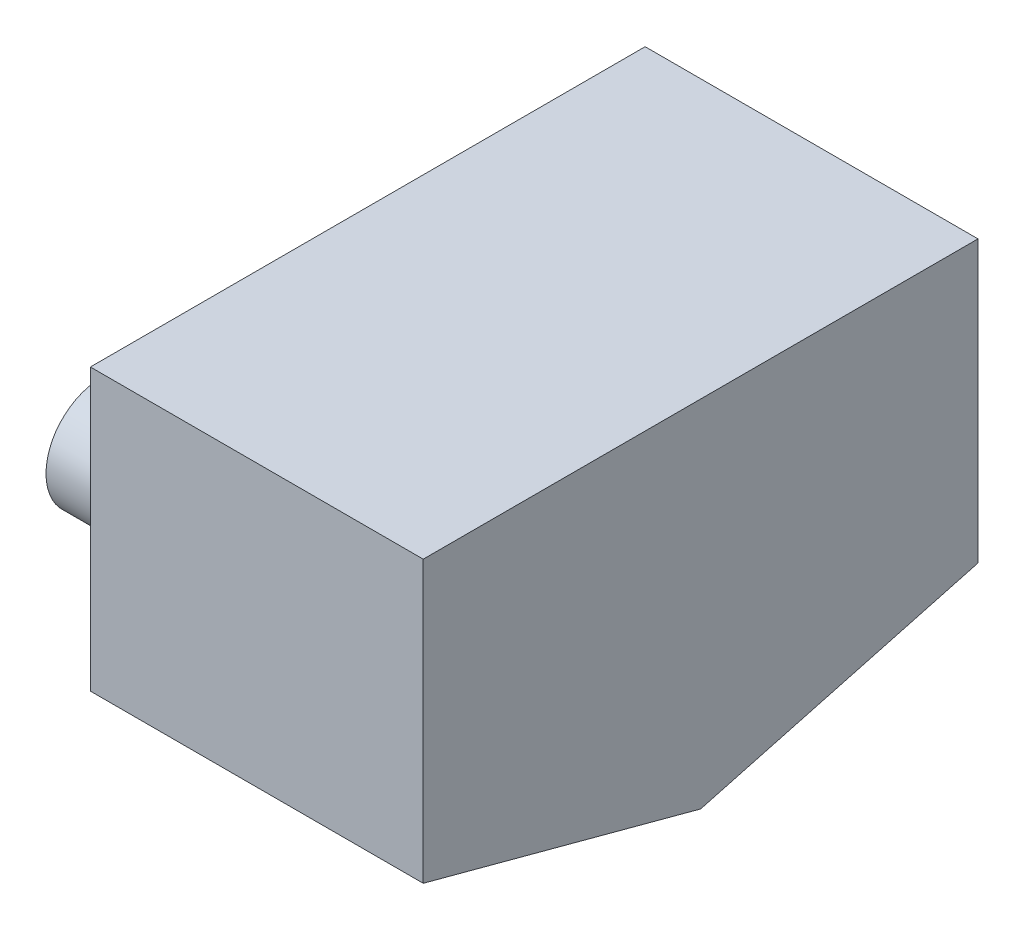
SolidWorks part; units mm, degrees
material "1060 Alloy"
ref_plane "Front Plane" through (0, 0, 0) normal (0, 0, 1) x (1, 0, 0)
ref_plane "Top Plane" through (0, 0, 0) normal (0, 1, 0) x (1, 0, 0)
ref_plane "Right Plane" through (0, 0, 0) normal (1, 0, 0) x (0, 0, -1)
sketch "Sketch2" plane through (0, 0, 0) normal (0, 0, 1) x (1, 0, 0)
  line L0 (0, 0) -> (15, 0)
  line L1 (15, 16) -> (0, 16)
  line L2 (15, 16) -> (15, 0)
  line L4 (0, 16) -> (0, 0)
  dimension "D1" = 16
  dimension "D2" = 15
extrude "Boss-Extrude2" add sketch "Sketch2" along normal blind 25
sketch "Sketch3" plane through (0, 0, 0) normal (-1, 0, 0) x (0, 0, 1)
  line L1 (0, 16) -> (0, 0) construction
  circle A0 centre (5.5, 7.8379) radius 2.5
  circle A1 centre (19.5, 7.8379) radius 2.5
  dimension "D1" = 5
  dimension "D2" = 5
  dimension "D4" = 14
  dimension "D3" = 5.5
extrude "Boss-Extrude3" add sketch "Sketch3" along normal blind 5
chamfer "Chamfer1" distance 12.5 angle 15 1 edges at (7.5, 0, 25) first distance on face at (7.5, 0, 12.5)
chamfer "Chamfer2" distance 12.5 angle 15 1 edges at (7.5, 0, 0) first distance on face at (7.5, 0, 6.25)
